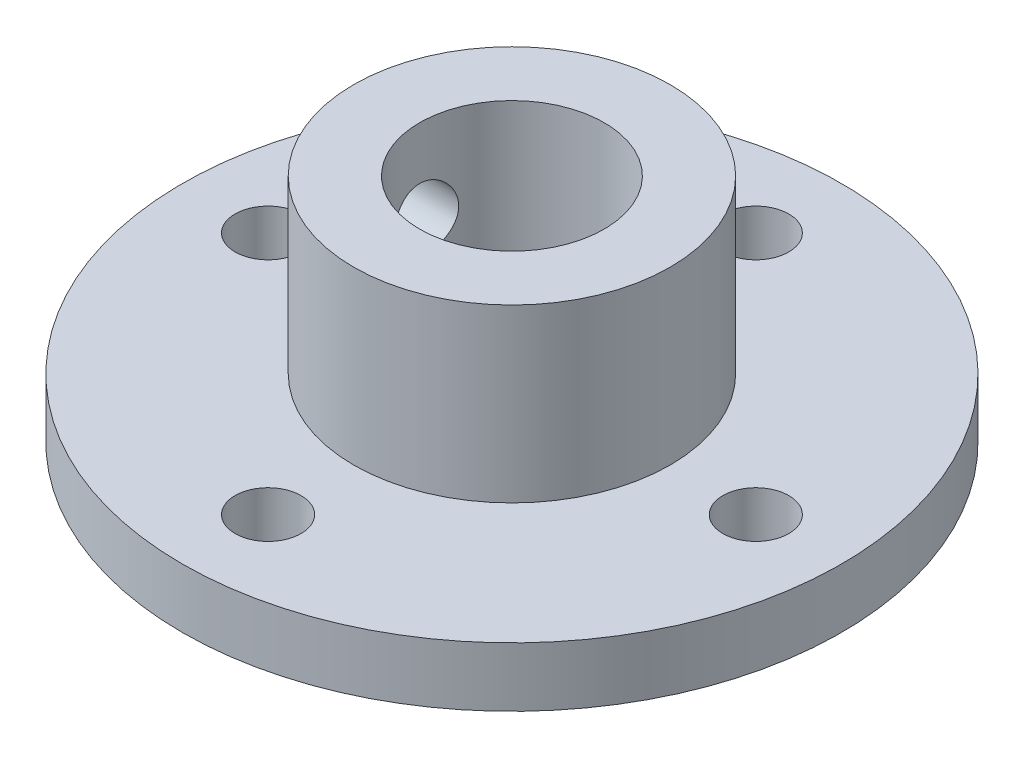
SolidWorks part; units mm, degrees
ref_plane "Front Plane" through (0, 0, 0) normal (0, 0, 1) x (1, 0, 0)
ref_plane "Top Plane" through (0, 0, 0) normal (0, 1, 0) x (1, 0, 0)
ref_plane "Right Plane" through (0, 0, 0) normal (1, 0, 0) x (0, 0, -1)
sketch "Sketch1" plane through (0, 0, 0) normal (0, 1, 0) x (1, 0, 0)
  circle A0 centre (0, 0) radius 25
  dimension "D1" = 50
extrude "Boss-Extrude1" add sketch "Sketch1" along normal blind 4.5
sketch "Sketch2" plane through (0, 4.5, 0) normal (0, 1, 0) x (1, 0, 0)
  circle A0 centre (0, 0) radius 12
  dimension "D1" = 24
extrude "Boss-Extrude2" add sketch "Sketch2" along normal blind 13
sketch "Sketch3" plane through (0, 17.5, 0) normal (0, 1, 0) x (1, 0, 0)
  circle A0 centre (0, 0) radius 7
  dimension "D1" = 14
extrude "Cut-Extrude1" cut sketch "Sketch3" against normal up to surface (17.5 mm away) up to face at (0, 0, 25)
sketch "Sketch4" plane through (0, 4.5, 0) normal (0, 1, 0) x (1, 0, 0)
  circle A0 centre (0, 0) radius 18.5 construction
  circle A1 centre (-18.5, 0) radius 2.5
  circle A2 centre (0, 18.5) radius 2.5
  circle A3 centre (18.5, 0) radius 2.5
  circle A4 centre (0, -18.5) radius 2.5
  dimension "D1" = 37
  dimension "D2" = 5
extrude "Cut-Extrude2" cut sketch "Sketch4" against normal up to surface (4.5 mm away) up to face at (0, 0, 7)
sketch "Sketch5" plane through (0, 0, 0) normal (1, 0, 0) x (0, 0, -1)
  line L0 (0, 17.5) -> (0, 4.5) construction
  line L1 (12, 17.5) -> (-12, 17.5) construction
  line L2 (25, 4.5) -> (-25, 4.5) construction
  circle A0 centre (0, 11) radius 2.5
  dimension "D1" = 5
extrude "Cut-Extrude3" cut sketch "Sketch5" against normal blind 25
